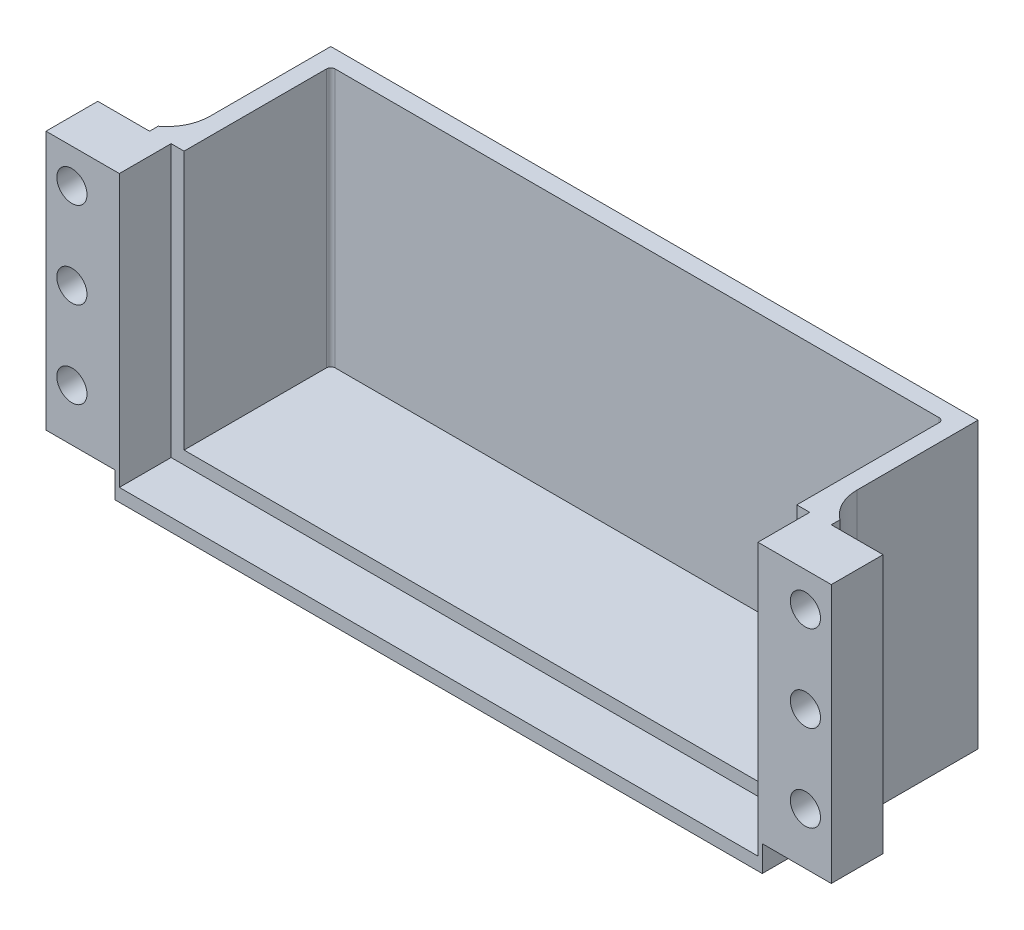
SolidWorks part; units mm, degrees
ref_plane "Front Plane" through (0, 0, 0) normal (0, 0, 1) x (1, 0, 0)
ref_plane "Top Plane" through (0, 0, 0) normal (0, 1, 0) x (1, 0, 0)
ref_plane "Right Plane" through (0, 0, 0) normal (1, 0, 0) x (0, 0, -1)
sketch "Sketch2" plane through (0, 0, 0) normal (0, 1, 0) x (1, 0, 0)
  line L0 (-37.5, 0) -> (37.5, 0) construction
  line L2 (-37.5, 0) -> (37.5, 0)
  line L3 (-37.5, 0) -> (-37.5, 25)
  line L4 (-37.5, 25) -> (37.5, 25)
  line L5 (37.5, 0) -> (37.5, 25)
  point P4 (0, 0)
  point P6 (0, 0)
  dimension "D1" = 25
extrude "Boss-Extrude1" add sketch "Sketch2" along normal blind 3
sketch "Sketch3" plane through (0, 3, 0) normal (0, 1, 0) x (1, 0, 0)
  line L0 (-12.5, 25) -> (-12.5, 0) construction
  line L1 (37.5, 25) -> (-37.5, 25) construction
  line L2 (-37.5, 0) -> (37.5, 0) construction
  line L3 (12.5, 25) -> (12.5, 0) construction
  line L6 (-35.5, 0) -> (-35.5, 23)
  line L7 (-35.5, 23) -> (35.5, 23)
  line L8 (35.5, 23) -> (35.5, 0)
  line L9 (-37.5, 25) -> (-37.5, 0) construction
  line L10 (37.5, 0) -> (37.5, 25) construction
  line L11 (-35.5, 0) -> (-37.5, 0)
  line L12 (-37.5, 0) -> (-37.5, 25)
  line L13 (-37.5, 25) -> (37.5, 25)
  line L14 (37.5, 25) -> (37.5, 0)
  line L15 (37.5, 0) -> (35.5, 0)
  dimension "D1" = 2
  dimension "D2" = 2
  dimension "D3" = 2
extrude "Boss-Extrude2" add sketch "Sketch3" along normal blind 30
sketch "Sketch5" plane through (-37.5, 0, 0) normal (-1, 0, 0) x (0, 0, 1)
  line L1 (0, 33) -> (-6, 33)
  line L2 (0, 33) -> (0, 3)
  line L3 (0, 3) -> (-6, 3)
  line L4 (-6, 33) -> (-6, 3)
  dimension "D1" = 6
  dimension "D2" = 30
extrude "Boss-Extrude3" add sketch "Sketch5" along normal blind 8
sketch "Sketch6" plane through (37.5, 0, 0) normal (1, 0, 0) x (0, 0, -1)
  line L1 (0, 33) -> (6, 33)
  line L2 (0, 33) -> (0, 3)
  line L3 (0, 3) -> (6, 3)
  line L4 (6, 33) -> (6, 3)
  dimension "D1" = 6
  dimension "D2" = 30
extrude "Boss-Extrude4" add sketch "Sketch6" along normal blind 8
sketch "Sketch8" plane through (0, 0, 0) normal (0, 0, 1) x (1, 0, 0)
  line L0 (-42.5, 3) -> (-42.5, 33) construction
  line L3 (-45.5, 3) -> (-37.5, 3) construction
  line L4 (-45.5, 33) -> (-35.5, 33) construction
  line L5 (42.5, 3) -> (42.5, 33) construction
  line L6 (45.5, 3) -> (37.5, 3) construction
  line L7 (35.5, 33) -> (45.5, 33) construction
  line L8 (-45.5, 3) -> (-45.5, 33) construction
  line L9 (45.5, 33) -> (45.5, 3) construction
  circle A0 centre (-42.5, 29) radius 1.75
  circle A1 centre (42.5, 29) radius 1.75
  circle A4 centre (-42.5, 19) radius 1.75
  circle A5 centre (-42.5, 9) radius 1.75
  circle A6 centre (42.5, 19) radius 1.75
  circle A7 centre (42.5, 9) radius 1.75
  dimension "D5" = 3.5
  dimension "D6" = 3.5
  dimension "D1" = 3
  dimension "D2" = 3
  dimension "D3" = 4
  dimension "D4" = 4
  dimension "D7" = 3
  dimension "D8" = 3
extrude "Cut-Extrude1" cut sketch "Sketch8" against normal blind 8
sketch "Sketch12" plane through (0, 0, 0) normal (0, 0, 1) x (1, 0, 0)
  line L0 (0, 0) -> (0, 3) construction
  line L1 (-35.5, 33) -> (-37, 33)
  line L2 (-35.5, 33) -> (-35.5, 3)
  line L4 (-37, 33) -> (-37, 1.5)
  line L5 (-35.5, 3) -> (35.5, 3) construction
  line L7 (37, 33) -> (37, 1.5)
  line L8 (35.5, 33) -> (37, 33)
  line L9 (35.5, 33) -> (35.5, 3)
  line L10 (-37, 1.5) -> (37, 1.5)
  line L11 (-35.5, 3) -> (35.5, 3)
  dimension "D1" = 1.5
  dimension "D2" = 31.5
extrude "Cut-Extrude2" cut sketch "Sketch12" against normal blind 6
fillet "Fillet1" radius 5 1 edges at (-37.5, 18, -6)
fillet "Fillet2" radius 5 1 edges at (37.5, 18, -6)
sketch "Sketch13" plane through (0, 33, 0) normal (0, 1, 0) x (1, 0, 0)
  line L0 (0, 25) -> (0, 23) construction
  line L5 (-45.5, 6) -> (-39.5, 6)
  line L6 (-45.5, 6) -> (-45.5, 8)
  line L7 (-45.5, 8) -> (-39.5, 8)
  line L8 (-39.5, 6) -> (-39.5, 8)
  line L9 (37.5, 25) -> (-37.5, 25) construction
  line L10 (-35.5, 23) -> (35.5, 23) construction
  line L11 (45.5, 8) -> (39.5, 8)
  line L12 (39.5, 6) -> (39.5, 8)
  line L13 (45.5, 6) -> (39.5, 6)
  line L14 (45.5, 6) -> (45.5, 8)
  dimension "D1" = 2
  dimension "D2" = 6
extrude "Cut-Extrude3" cut sketch "Sketch13" against normal blind 36
fillet "Fillet3" radius 0.5 2 edges at (-35.5, 18, -23) (35.5, 18, -23)
